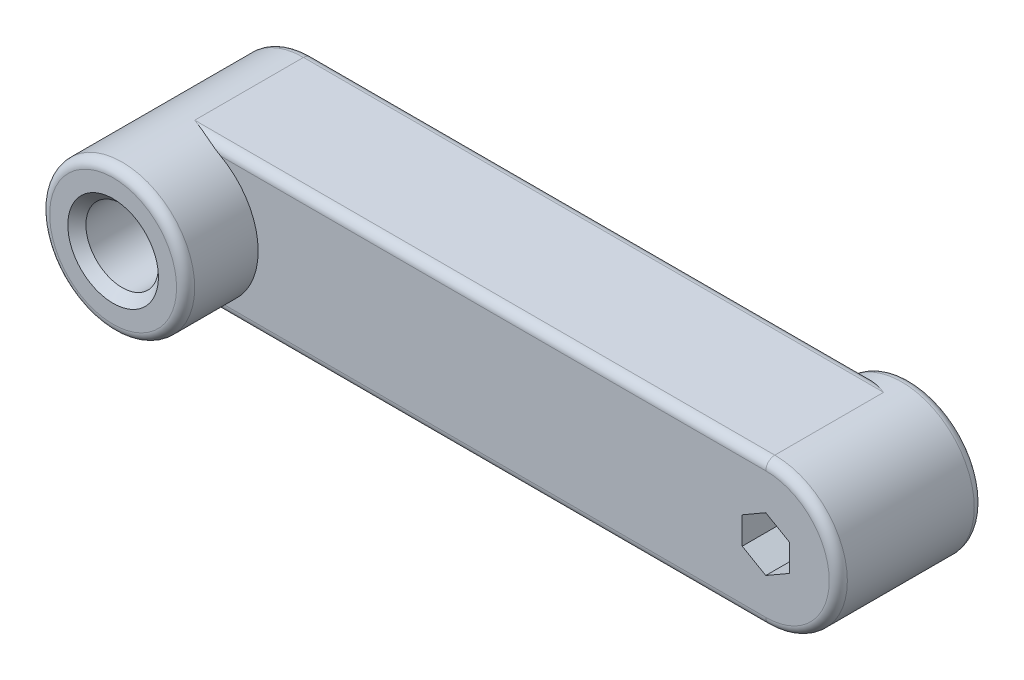
SolidWorks part; units mm, degrees
ref_plane "Plano frontal" through (0, 0, 0) normal (0, 0, 1) x (1, 0, 0)
ref_plane "Plano superior" through (0, 0, 0) normal (0, 1, 0) x (1, 0, 0)
ref_plane "Plano direito" through (0, 0, 0) normal (1, 0, 0) x (0, 0, -1)
sketch "Esboço1" plane through (0, 0, 0) normal (0, 0, 1) x (1, 0, 0)
  line L0 (-32, 0) -> (0, 0) construction
  line L1 (0, 0) -> (-32, 0) construction
  line L2 (0, 1.5) -> (-1.2991, 0.75)
  line L3 (-1.2991, 0.75) -> (-1.2991, -0.75)
  line L4 (-1.2991, -0.75) -> (0, -1.5)
  line L5 (0, -1.5) -> (1.2991, -0.75)
  line L6 (1.2991, -0.75) -> (1.2991, 0.75)
  line L7 (1.2991, 0.75) -> (0, 1.5)
  line L8 (0, -4) -> (-32, -4)
  line L9 (0, 4) -> (-32, 4)
  circle A0 centre (0, 0) radius 3 construction
  circle A1 centre (-32, 0) radius 2
  circle A3 centre (0, 0) radius 1.2991 construction
  arc A4 (0, -4) -> (0, 4) centre (0, 0) ccw
  arc A5 (-32, 4) -> (-32, -4) centre (-32, 0) ccw
  point P6 (-16, 0)
  dimension "D1" = 6
  dimension "D4" = 4
  dimension "D6" = 4
  dimension "D2" = 32
  dimension "D5" = 2.5981
extrude "Ressalto-extrusão1" add sketch "Esboço1" along normal blind 12
sketch "Esboço2" plane through (0, 0, 0) normal (0, 0, -1) x (-1, 0, 0)
  circle A0 centre (0, 0) radius 4
extrude "Corte-extrusão1" cut sketch "Esboço2" against normal blind 1 flip side to cut
sketch "Esboço3" plane through (0, 0, 12) normal (0, 0, 1) x (1, 0, 0)
  circle A0 centre (-32, 0) radius 4
extrude "Corte-extrusão2" cut sketch "Esboço3" against normal blind 4 flip side to cut
fillet "Filete1" radius 0.5 8 edges at (-16, -4, 1) (-36, 0, 1) (-28, 0, 12) (4, 0, 0) (-16, 4, 1) (-16, 4, 8) (4, 0, 8) (-16, -4, 8)
chamfer "Chanfro1" distance 0.5 angle 45 2 edges at (-34, 0, 1) (-30, 0, 12)
